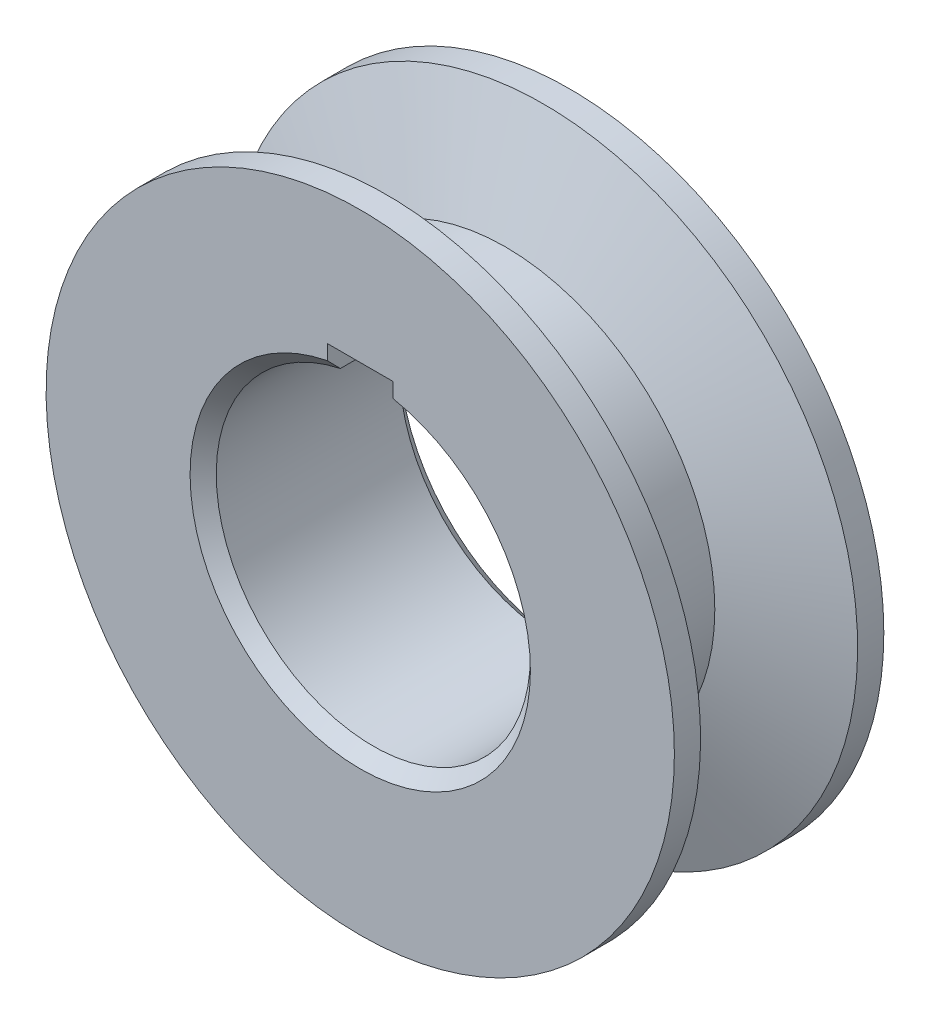
SolidWorks part; units mm, degrees
material "6061-T6 (SS)"
ref_plane "Front Plane" through (0, 0, 0) normal (0, 0, 1) x (1, 0, 0)
ref_plane "Top Plane" through (0, 0, 0) normal (0, 1, 0) x (1, 0, 0)
ref_plane "Right Plane" through (0, 0, 0) normal (1, 0, 0) x (0, 0, -1)
sketch "Sketch1" plane through (0, 0, 0) normal (0, 0, 1) x (1, 0, 0)
  circle A0 centre (0, 0) radius 19.05
  circle A1 centre (0, 0) radius 9.525
  dimension "D1" = 38.1
  dimension "D2" = 19.05
extrude "Extrude1" add sketch "Sketch1" along normal mid plane 12.7
sketch "Sketch2" plane through (0, 0, 0) normal (1, 0, 0) x (0, 0, -1)
  line L0 (-4.7625, 19.05) -> (4.7625, 19.05)
  line L2 (4.7625, 19.05) -> (2.4513, 12.7)
  line L3 (2.4513, 12.7) -> (-2.4513, 12.7)
  line L4 (-2.4513, 12.7) -> (-4.7625, 19.05)
  line L5 (-6.35, 0) -> (6.35, 0) construction
  line L6 (-6.35, 19.05) -> (-6.35, -19.05) construction
  line L7 (6.35, -19.05) -> (6.35, 19.05) construction
  point P2 (0, 19.05)
  point P5 (0, 12.7)
  dimension "D1" = 19.05
  dimension "D2" = 6.35
  dimension "D3" = 9.525
  dimension "D4" = 40
chamfer "Chamfer1" distance 0.7937 angle 45 2 edges at (9.525, 0, -6.35) (9.525, 0, 6.35)
revolve "Cut-Revolve1" cut sketch "Sketch2" angle 360 about L5
sketch "Sketch3" plane through (0, 0, -6.35) normal (0, 0, -1) x (-1, 0, 0)
  line L0 (0, 0) -> (0, 9.525) construction
  line L1 (-2, 11.025) -> (2, 11.025)
  line L2 (-2, 11.025) -> (-2, 8.025)
  line L3 (-2, 8.025) -> (2, 8.025)
  line L4 (2, 11.025) -> (2, 8.025)
  line L5 (-2, 11.025) -> (2, 8.025) construction
  line L6 (-2, 8.025) -> (2, 11.025) construction
  circle A0 centre (0, 0) radius 9.525 construction
  point P0 (0, 9.525)
  dimension "D1" = 4
  dimension "D2" = 3
extrude "Cut-Extrude1" cut sketch "Sketch3" against normal through all
